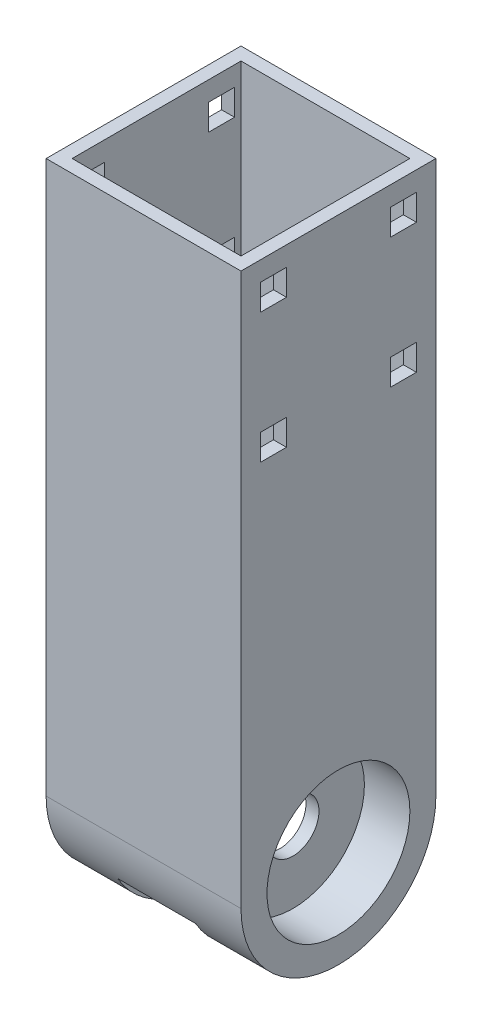
SolidWorks part; units mm, degrees
ref_plane "Front Plane" through (0, 0, 0) normal (0, 0, 1) x (1, 0, 0)
ref_plane "Top Plane" through (0, 0, 0) normal (0, 1, 0) x (1, 0, 0)
ref_plane "Right Plane" through (0, 0, 0) normal (1, 0, 0) x (0, 0, -1)
sketch "Sketch1" plane through (0, 0, 0) normal (0, 1, 0) x (1, 0, 0)
  line L1 (-15, -15) -> (15, -15)
  line L2 (-15, -15) -> (-15, 15)
  line L3 (-15, 15) -> (15, 15)
  line L4 (15, -15) -> (15, 15)
  line L5 (-15, -15) -> (15, 15) construction
  line L6 (-15, 15) -> (15, -15) construction
  line L11 (-6, -6) -> (6, 6) construction
  line L12 (-6, 6) -> (6, -6) construction
  line L13 (-6, -13) -> (6, -13)
  line L14 (-6, -13) -> (-6, 13)
  line L15 (-6, 13) -> (6, 13)
  line L16 (6, -13) -> (6, 13)
  line L17 (-6, -13) -> (6, 13) construction
  line L18 (-6, 13) -> (6, -13) construction
  point P0 (0, 0)
  point P6 (0, 0)
  point P11 (0, 0)
  dimension "D1" = 30
  dimension "D2" = 30
  dimension "D3" = 9
  dimension "D4" = 2
extrude "Boss-Extrude2" add sketch "Sketch1" along normal blind 100
sketch "Sketch2" plane through (15, 0, 0) normal (1, 0, 0) x (0, 0, -1)
  line L0 (-15, 95) -> (15, 95)
  line L1 (-15, 100) -> (-15, 0) construction
  line L2 (15, 100) -> (15, 0) construction
  line L3 (-15, 100) -> (15, 100) construction
  line L4 (-15, 100) -> (-15, 70) construction
  line L5 (-15, 70) -> (15, 70) construction
  line L6 (-15, 70) -> (15, 70)
  line L8 (-12, 93) -> (-8, 93)
  line L9 (-12, 93) -> (-12, 97)
  line L10 (-12, 97) -> (-8, 97)
  line L11 (-8, 93) -> (-8, 97)
  line L12 (-12, 93) -> (-8, 97) construction
  line L13 (-12, 97) -> (-8, 93) construction
  line L14 (12, 97) -> (8, 97)
  line L15 (12, 97) -> (12, 93)
  line L16 (12, 93) -> (8, 93)
  line L17 (8, 97) -> (8, 93)
  line L18 (12, 97) -> (8, 93) construction
  line L19 (12, 93) -> (8, 97) construction
  line L20 (-12, 73) -> (-8, 73)
  line L21 (-12, 73) -> (-12, 77)
  line L22 (-12, 77) -> (-8, 77)
  line L23 (-8, 73) -> (-8, 77)
  line L24 (-12, 73) -> (-8, 77) construction
  line L25 (-12, 77) -> (-8, 73) construction
  line L26 (8, 73) -> (12, 73)
  line L27 (8, 73) -> (8, 77)
  line L28 (8, 77) -> (12, 77)
  line L29 (12, 73) -> (12, 77)
  line L30 (8, 73) -> (12, 77) construction
  line L31 (8, 77) -> (12, 73) construction
  circle A0 centre (-10, 95) radius 2
  circle A1 centre (10, 95) radius 2
  circle A4 centre (-10, 75) radius 2
  circle A5 centre (10, 75) radius 2
  dimension "D2" = 4
  dimension "D4" = 4
  dimension "D7" = 5
  dimension "D8" = 4
  dimension "D9" = 5
  dimension "D11" = 4
  dimension "D13" = 4
  dimension "D1" = 5
  dimension "D3" = 5
  dimension "D5" = 5
  dimension "D6" = 30
  dimension "D10" = 5
  dimension "D12" = 5
  dimension "D14" = 4
  dimension "D15" = 4
  dimension "D16" = 4
  dimension "D17" = 4
  dimension "D18" = 4
extrude "Cut-Extrude1" cut sketch "Sketch2" against normal blind 51 contours L16 L17 L14 L15 | L11 L10 L9 L8 | L23 L22 L21 L20 | L28 L29 L26 L27
sketch "Sketch3" plane through (0, 100, 0) normal (0, 1, 0) x (1, 0, 0)
  line L0 (-6, 13) -> (-13, 13)
  line L1 (-15, 15) -> (-15, -15) construction
  line L2 (-13, 13) -> (-13, -13)
  line L7 (-6, -13) -> (-13, -13)
  line L8 (-6, 13) -> (-6, -13)
  line L9 (15, -15) -> (15, 15) construction
  line L10 (6, 13) -> (13, 13)
  line L11 (6, 13) -> (6, -13)
  line L12 (6, -13) -> (13, -13)
  line L13 (13, 13) -> (13, -13)
  dimension "D1" = 2
  dimension "D2" = 2
extrude "Cut-Extrude2" cut sketch "Sketch3" against normal blind 70
fillet "Fillet1" radius 15 2 edges at (0, 0, -15) (0, 0, 15)
sketch "Sketch5" plane through (15, 0, 0) normal (1, 0, 0) x (0, 0, -1)
  circle A0 centre (0, 15) radius 4
  dimension "D1" = 8
extrude "Cut-Extrude3" cut sketch "Sketch5" against normal blind 50
sketch "Sketch6" plane through (15, 0, 0) normal (1, 0, 0) x (0, 0, -1)
  circle A0 centre (0, 15) radius 11
  dimension "D1" = 22
extrude "Cut-Extrude4" cut sketch "Sketch6" against normal blind 7
sketch "Sketch7" plane through (-15, 0, 0) normal (-1, 0, 0) x (0, 0, 1)
  circle A0 centre (0, 15) radius 11
  dimension "D1" = 22
extrude "Cut-Extrude5" cut sketch "Sketch7" against normal blind 7
